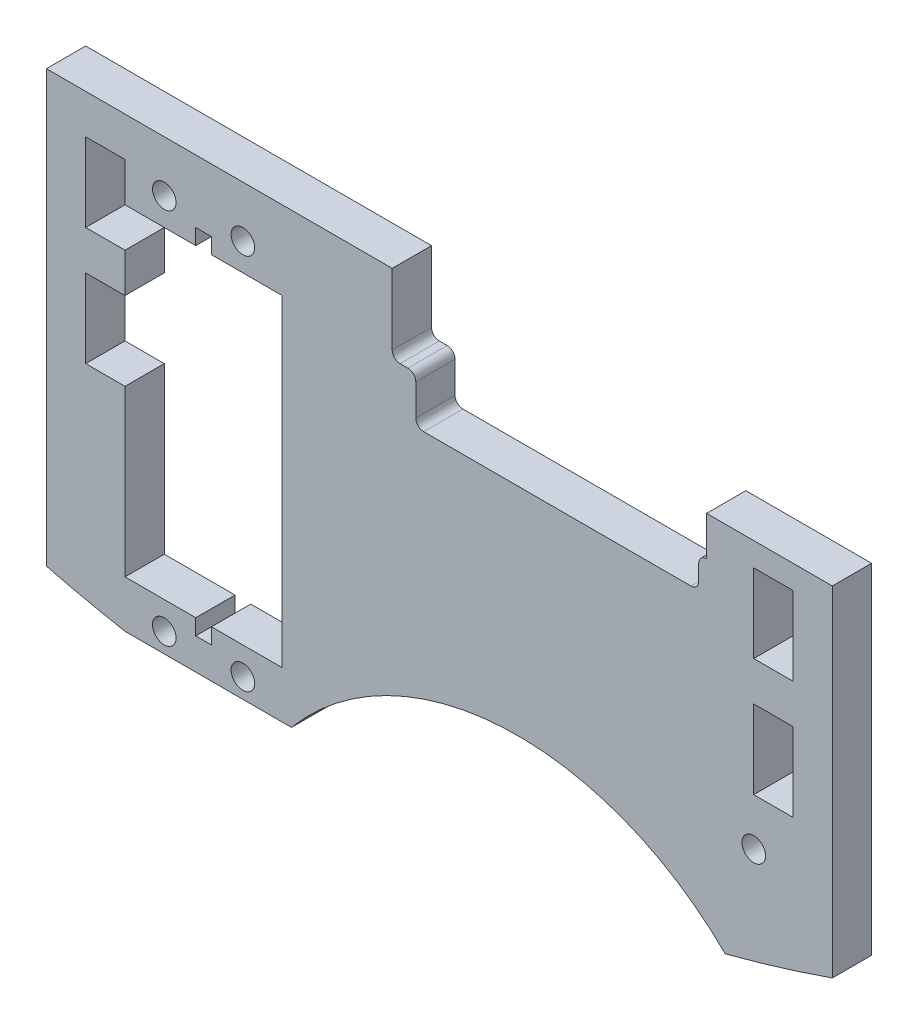
SolidWorks part; units mm, degrees
ref_plane "Plan de face" through (0, 0, 0) normal (0, 0, 1) x (1, 0, 0)
ref_plane "Plan de dessus" through (0, 0, 0) normal (0, 1, 0) x (1, 0, 0)
ref_plane "Plan de droite" through (0, 0, 0) normal (1, 0, 0) x (0, 0, -1)
sketch "Esquisse1" plane through (0, 0, 0) normal (0, 0, 1) x (1, 0, 0)
  line L0 (20, 67) -> (20, -4) construction
  line L1 (0, 0) -> (31.1859, 0)
  line L2 (0, 0) -> (0, 57)
  line L3 (0, 57) -> (44, 57)
  line L4 (100, 0) -> (100, 50)
  line L5 (10, 26.5) -> (30, 26.5) construction
  line L6 (10, 47) -> (19, 47)
  line L7 (10, 42) -> (10, 37)
  line L8 (10, 6) -> (19, 6)
  line L9 (30, 47) -> (30, 6)
  line L10 (20, 16) -> (90, 16) construction
  line L11 (88.8141, 0) -> (100, 0)
  line L12 (21, 4) -> (21, 6)
  line L13 (19, 49) -> (21, 49)
  line L14 (19, 49) -> (19, 47)
  line L15 (21, 6) -> (30, 6)
  line L16 (21, 49) -> (21, 47)
  line L17 (19, 4) -> (21, 4)
  line L18 (19, 4) -> (19, 6)
  line L19 (21, 47) -> (30, 47)
  line L20 (10, 27) -> (10, 6)
  line L21 (90, 47) -> (95, 47)
  line L22 (90, 47) -> (90, 37)
  line L23 (90, 37) -> (95, 37)
  line L24 (95, 47) -> (95, 37)
  line L25 (90, 32) -> (95, 32)
  line L26 (90, 32) -> (90, 22)
  line L27 (90, 22) -> (95, 22)
  line L28 (95, 32) -> (95, 22)
  line L29 (5, 52) -> (10, 52)
  line L30 (5, 52) -> (5, 42)
  line L31 (5, 42) -> (10, 42)
  line L32 (10, 52) -> (10, 47)
  line L33 (5, 37) -> (10, 37)
  line L34 (5, 37) -> (5, 27)
  line L35 (5, 27) -> (10, 27)
  line L36 (84, 50) -> (100, 50)
  line L37 (47, 47) -> (44, 47)
  line L38 (84, 50) -> (84, 45)
  line L39 (84, 45) -> (83, 45)
  line L40 (44, 57) -> (44, 47)
  line L42 (83, 45) -> (83, 41)
  line L43 (83, 41) -> (47, 41)
  line L44 (47, 47) -> (47, 41)
  circle A0 centre (15, 2.5) radius 1.5
  circle A1 centre (25, 2.5) radius 1.5
  circle A2 centre (25, 50.5) radius 1.5
  circle A3 centre (15, 50.5) radius 1.5
  circle A4 centre (20, 16) radius 1.5 construction
  circle A5 centre (20, 16) radius 1.5 construction
  circle A6 centre (90, 16) radius 1.5
  circle A7 centre (60, -24) radius 37.5 construction
  arc A8 (31.1859, 0) -> (88.8141, 0) centre (60, -24) cw
  dimension "D6" = 3.5
  dimension "D8" = 3
  dimension "D9" = 3
  dimension "D10" = 70
  dimension "D13" = 75
  dimension "D16" = 2
  dimension "D1" = 6
  dimension "D2" = 41
  dimension "D3" = 20
  dimension "D4" = 10
  dimension "D5" = 100
  dimension "D7" = 5
  dimension "D11" = 10
  dimension "D12" = 10
  dimension "D14" = 40
  dimension "D15" = 40
  dimension "D17" = 2
  dimension "D18" = 5
  dimension "D19" = 5
  dimension "D20" = 10
  dimension "D21" = 3
  dimension "D22" = 5
  dimension "D23" = 5
  dimension "D24" = 10
  dimension "D25" = 6
  dimension "D26" = 10
  dimension "D27" = 40
  dimension "D28" = 1
  dimension "D29" = 36
  dimension "D30" = 5
  dimension "D31" = 5
  dimension "D32" = 4
  dimension "D33" = 5
  dimension "D34" = 50
extrude "Boss.-Extru.1" add sketch "Esquisse1" along normal blind 5
fillet "Congé1" radius 1 5 edges at (83, 45, 2.5) (83, 41, 2.5) (47, 41, 2.5) (47, 47, 2.5) (44, 47, 2.5)
sketch "Esquisse2" plane through (0, 0, 5) normal (0, 0, 1) x (1, 0, 0)
  line L0 (0, 0) -> (31.1859, 0) construction
  line L1 (10, 27) -> (10, 6) construction
  line L2 (-40.4936, 0.9705) -> (-34.879, 14.9208)
  line L3 (159.5405, 42.1102) -> (167.1741, 28.8302)
  arc A0 (-34.879, 14.9208) -> (159.5405, 42.1102) centre (42.2645, 172) ccw
  arc A1 (-40.4936, 0.9705) -> (167.1741, 28.8302) centre (42.2645, 172) ccw
  point P3 (10, 0)
  dimension "D1" = 175
  dimension "D2" = 15
  dimension "D3" = 172
extrude "Enlèv. mat.-Extru.1" cut sketch "Esquisse2" against normal blind 10
